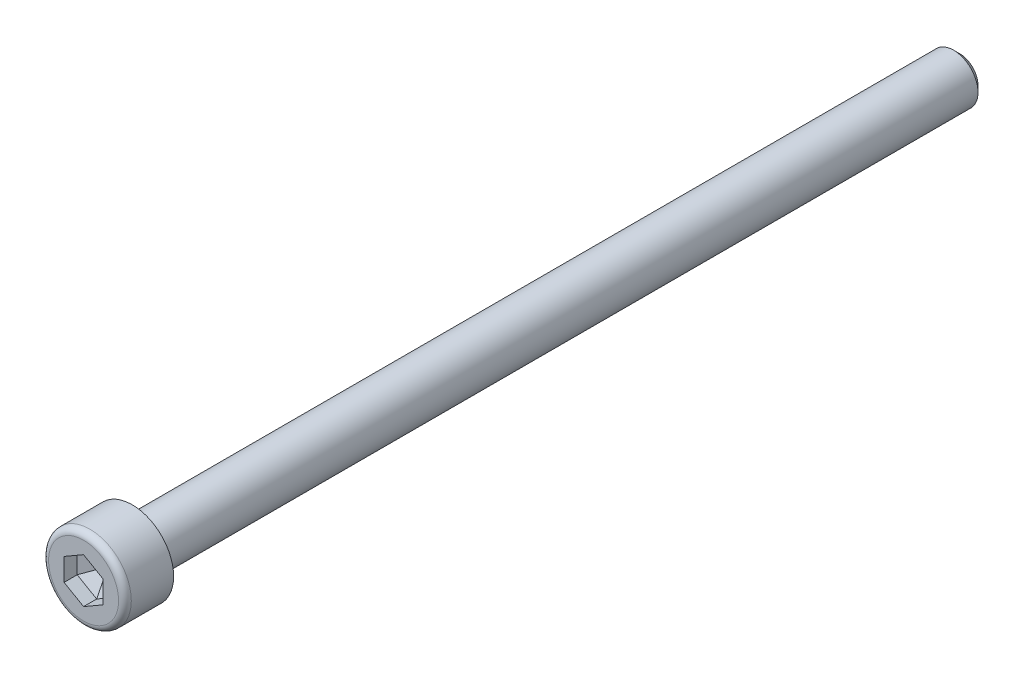
SolidWorks part; units mm, degrees
material "普通碳钢"
ref_plane "前视基准面" through (0, 0, 0) normal (0, 0, 1) x (1, 0, 0)
ref_plane "上视基准面" through (0, 0, 0) normal (0, 1, 0) x (1, 0, 0)
ref_plane "右视基准面" through (0, 0, 0) normal (1, 0, 0) x (0, 0, -1)
sketch "草图1" plane through (0, 0, 0) normal (0, 0, 1) x (1, 0, 0)
  circle A0 centre (0, 0) radius 4.25
  dimension "dk" = 8.5
extrude "凸台-拉伸1" add sketch "草图1" along normal blind 5
ref_axis "基准轴1" through (0, 0, 5) along (0, 0, -1)
sketch "草图2" plane through (0, 0, 5) normal (0, 0, 1) x (1, 0, 0)
  line L1 (2, 1.1547) -> (0, 2.3094)
  line L2 (0, 2.3094) -> (-2, 1.1547)
  line L3 (-2, 1.1547) -> (-2, -1.1547)
  line L4 (-2, -1.1547) -> (0, -2.3094)
  line L5 (0, -2.3094) -> (2, -1.1547)
  line L6 (2, -1.1547) -> (2, 1.1547)
  circle A0 centre (0, 0) radius 2 construction
  dimension "s" = 4
extrude "切除-拉伸1" cut sketch "草图2" against normal blind 2.5
sketch "草图3" plane through (0, 0, 0) normal (0, 0, -1) x (-1, 0, 0)
  circle A0 centre (0, 0) radius 2.5
  dimension "d" = 5
extrude "凸台-拉伸2" add sketch "草图3" along normal blind 85
cosmetic thread "装饰螺纹线1" parameters "b"=4.9, "D2"=1.221
chamfer "倒角1" distance 0.625 angle 45 1 edges at (-2.5, 0, -85)
fillet "圆角1" radius 0.6538 1 edges at (4.25, 0, 5)
chamfer "倒角2" distance 1.1527 angle 60 6 edges at (-2, 0, 2.5) (-1, 1.7321, 2.5) (1, 1.7321, 2.5) (2, 0, 2.5) (-1, -1.7321, 2.5) (1, -1.7321, 2.5) first distance on face at (-2, 0, 3.75) first distance on face at (-1, 1.7321, 3.75) first distance on face at (1, 1.7321, 3.75) first distance on face at (2, 0, 3.75) first distance on face at (-1, -1.7321, 3.75) first distance on face at (1, -1.7321, 3.75)
fillet "圆角2" radius 0.1 1 edges at (2.5, 0, 0)
ref_plane "基准面1" through (0, 0, 0) normal (0, 0, -1) x (-1, 0, 0)
equation "\"D1@倒角2\" = \"s@草图2\" / 3.47"
equation "\"D1@圆角1\"= \"dk@草图1\" / 13"
equation "\"D1@倒角1\"= \"d@草图3\" / 8"
equation "\"D1@圆角2\"= \"d@草图3\" / \"d@草图3\" * 0.1"
